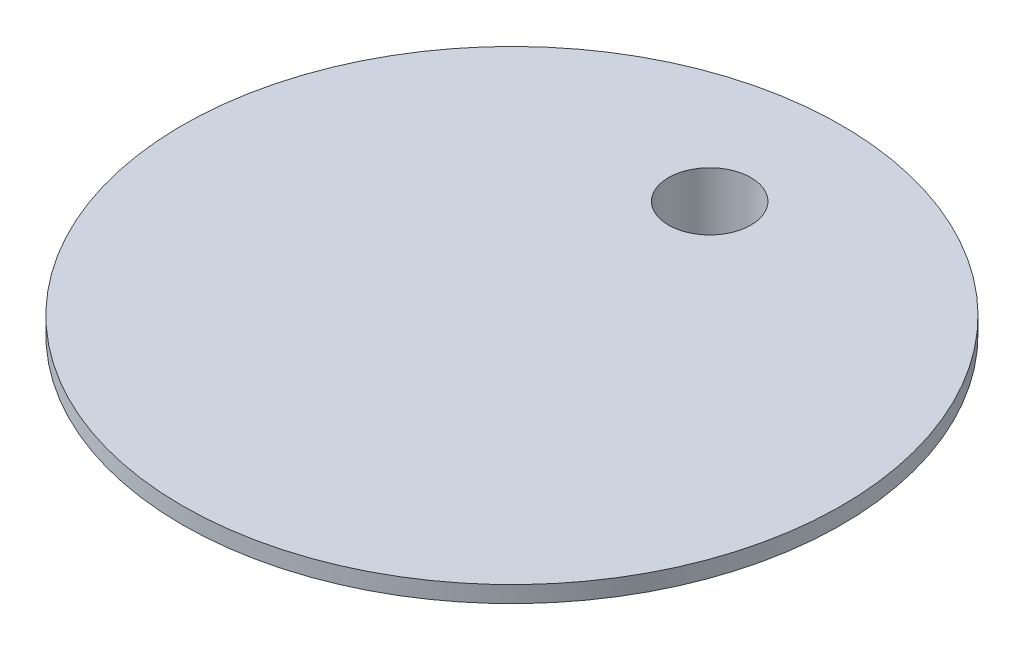
SolidWorks part; units mm, degrees
ref_plane "Front" through (0, 0, 0) normal (0, 0, 1) x (1, 0, 0)
ref_plane "Top" through (0, 0, 0) normal (0, 1, 0) x (1, 0, 0)
ref_plane "Right" through (0, 0, 0) normal (1, 0, 0) x (0, 0, -1)
sketch "Sketch1" plane through (0, 0, 0) normal (0, 1, 0) x (1, 0, 0)
  line L0 (0, 0) -> (0, 200) construction
  circle A0 centre (0, 0) radius 200
  circle A1 centre (0, 120) radius 25
  dimension "D3" = 50
  dimension "D4" = 120
extrude "Boss-Extrude1" add sketch "Sketch1" along normal blind 10
sketch "Sketch2" plane through (0, 0, 0) normal (0, -1, 0) x (1, 0, 0)
  circle A0 centre (0, -120) radius 25
  circle A1 centre (0, -120) radius 30
  dimension "D1" = 5
extrude "Boss-Extrude2" add sketch "Sketch2" along normal blind 85
